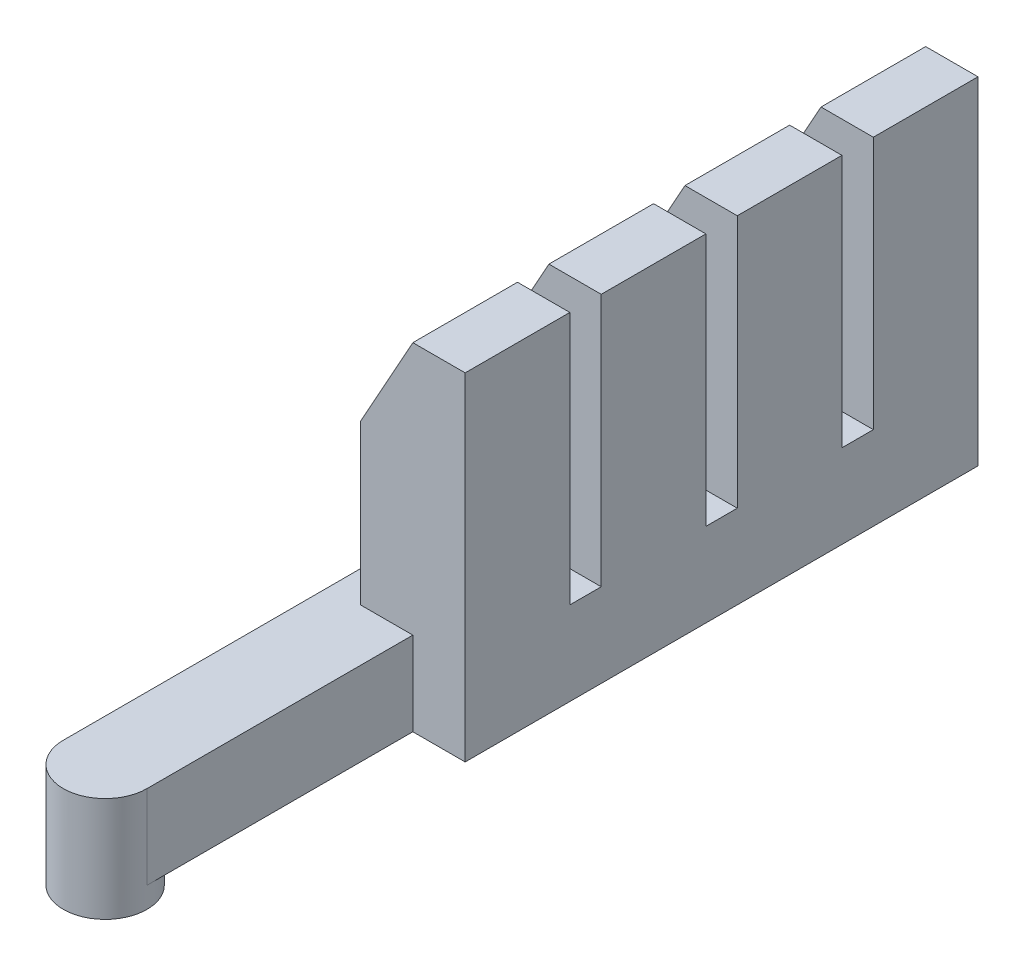
SolidWorks part; units mm, degrees
ref_plane "Front Plane" through (0, 0, 0) normal (0, 0, 1) x (1, 0, 0)
ref_plane "Top Plane" through (0, 0, 0) normal (0, 1, 0) x (1, 0, 0)
ref_plane "Right Plane" through (0, 0, 0) normal (1, 0, 0) x (0, 0, -1)
sketch "Sketch2" plane through (0, 0, 0) normal (0, 1, 0) x (1, 0, 0)
  circle A0 centre (0, 0) radius 20
  circle A1 centre (0, 0) radius 10
  dimension "D1" = 40
  dimension "D2" = 20
extrude "Boss-Extrude1" add sketch "Sketch2" along normal blind 80
sketch "Sketch3" plane through (0, 80, 0) normal (0, 1, 0) x (1, 0, 0)
  circle A0 centre (0, 0) radius 20
extrude "Boss-Extrude2" add sketch "Sketch3" along normal blind 5
sketch "Sketch4" plane through (0, 0, 0) normal (0, 0, 1) x (1, 0, 0)
  line L1 (20, 85) -> (-20, 85)
  line L2 (20, 85) -> (20, 45)
  line L3 (20, 45) -> (-20, 45)
  line L4 (-20, 85) -> (-20, 45)
  line L6 (15, 80) -> (-15, 80)
  line L7 (15, 80) -> (15, 50)
  line L8 (15, 50) -> (-15, 50)
  line L9 (-15, 80) -> (-15, 50)
  dimension "D1" = 40
  dimension "D2" = 5
  dimension "D3" = 5
  dimension "D4" = 5
  dimension "D5" = 5
extrude "Cut-Extrude1" cut sketch "Sketch4" against normal blind 50 contours L6 L9 L8 L7 | L7 L6 L9 L8 region at (0, 65, 0)
extrude "Boss-Extrude3" add sketch "Sketch4<4>" against normal blind 127 contours L1 L4 L3 L2 L9 L6 L7 L8 region at (19.4343, 65, 0)
sketch "Sketch4<4>" plane through (0, 0, 0) normal (0, 0, 1) x (1, 0, 0) same geometry as "Sketch4"
extrude "Cut-Extrude2" cut sketch "Sketch4<5>" along normal blind 10 contours L6 L9 L8 L7 region at (0, 65, 0)
sketch "Sketch4<5>" plane through (0, 0, 0) normal (0, 0, 1) x (1, 0, 0) same geometry as "Sketch4"
sketch "Sketch5" plane through (0, 0, 0) normal (0, -1, 0) x (1, 0, 0)
  circle A0 centre (0, 0) radius 10
extrude "Cut-Extrude3" cut sketch "Sketch5" against normal blind 50
sketch "Sketch6" plane through (0, 0, -127) normal (0, 0, -1) x (-1, 0, 0)
  line L0 (0, 80) -> (0, 85)
  line L1 (-15, 80) -> (15, 80) construction
  line L2 (-20, 85) -> (20, 85) construction
  line L3 (0, 85) -> (20, 85)
  line L4 (20, 85) -> (20, 45)
  line L5 (-20, 45) -> (20, 45) construction
  line L6 (-20, 45) -> (20, 45) construction
  line L7 (20, 45) -> (-45, 45)
  line L8 (-45, 45) -> (-45, 85)
  line L9 (-45, 85) -> (-40, 85)
  line L10 (-40, 85) -> (-40, 49.7955)
  line L11 (-40, 49.7955) -> (15, 50)
  line L12 (15, 50) -> (15, 80)
  line L13 (15, 80) -> (0, 80)
  dimension "D1" = 65
  dimension "D2" = 5
extrude "Boss-Extrude4" add sketch "Sketch6" along normal blind 245
sketch "Sketch7" plane through (0.1857, 49.9435, 0) normal (0.0037, 1, 0) x (1, -0.0037, 0)
  line L0 (-15.1858, 372) -> (-15.1858, 127) construction
  line L5 (39.8146, 127) -> (14.8146, 127)
  line L6 (39.8146, 127) -> (39.8146, 132)
  line L7 (39.8146, 132) -> (14.8146, 132)
  line L8 (14.8146, 127) -> (14.8146, 132)
  line L9 (39.8146, 372) -> (-15.1858, 372)
  line L10 (39.8146, 372) -> (39.8146, 367)
  line L11 (39.8146, 367) -> (-15.1858, 367)
  line L12 (-15.1858, 372) -> (-15.1858, 367)
  dimension "D1" = 25
  dimension "D2" = 5
  dimension "D3" = 5
extrude "Boss-Extrude5" add sketch "Sketch7" along normal blind 35
sketch "Sketch9" plane through (0, 85, 0) normal (0, 1, 0) x (1, 0, 0)
  line L1 (-5, 177) -> (45, 177)
  line L2 (-5, 177) -> (-5, 127)
  line L3 (-5, 127) -> (45, 127)
  line L4 (45, 177) -> (45, 127)
  line L5 (45, 372) -> (45, 127) construction
  line L6 (-5, 242) -> (45, 242)
  line L7 (-5, 242) -> (-5, 192)
  line L8 (-5, 192) -> (45, 192)
  line L9 (45, 242) -> (45, 192)
  line L11 (-5, 307) -> (45, 307)
  line L12 (-5, 307) -> (-5, 257)
  line L13 (-5, 257) -> (45, 257)
  line L14 (45, 307) -> (45, 257)
  line L15 (-5, 372) -> (45, 372)
  line L16 (-5, 372) -> (-5, 322)
  line L17 (-5, 322) -> (45, 322)
  line L18 (45, 372) -> (45, 322)
  line L19 (0, 172) -> (40, 172)
  line L20 (0, 172) -> (0, 132)
  line L21 (0, 132) -> (40, 132)
  line L22 (40, 172) -> (40, 132)
  line L23 (0, 237) -> (40, 237)
  line L24 (0, 237) -> (0, 197)
  line L25 (0, 197) -> (40, 197)
  line L26 (40, 237) -> (40, 197)
  line L27 (0, 302) -> (40, 302)
  line L28 (0, 302) -> (0, 262)
  line L29 (0, 262) -> (40, 262)
  line L30 (40, 302) -> (40, 262)
  line L31 (0, 367) -> (40, 367)
  line L32 (0, 367) -> (0, 327)
  line L33 (0, 327) -> (40, 327)
  line L34 (40, 367) -> (40, 327)
  line M36 (0, 127) -> (0, 372)
  dimension "D1" = 50
  dimension "D2" = 50
  dimension "D3" = 50
  dimension "D4" = 50
  dimension "D5" = 15
  dimension "D6" = 15
  dimension "D7" = 5
  dimension "D8" = 5
  dimension "D9" = 5
  dimension "D10" = 5
  dimension "D11" = 5
  dimension "D12" = 40
  dimension "D13" = 5
  dimension "D14" = 50
  dimension "D15" = 50
  dimension "D16" = 40
  dimension "D17" = 50
  dimension "D18" = 40
  dimension "D19" = 5
  dimension "D20" = 5
  dimension "D21" = 5
  dimension "D22" = 50
  dimension "D23" = 5
  dimension "D24" = 5
  dimension "D25" = 5
  dimension "D26" = 5
sketch "Sketch10" plane through (40, 0, 0) normal (-1, 0, 0) x (0, 0, 1)
  line L0 (-132, 84.7957) -> (-132, 49.7955) construction
  line L1 (-172, 85) -> (-197, 85)
  line L2 (-172, 85) -> (-172, 80)
  line L3 (-172, 80) -> (-197, 80)
  line L4 (-197, 85) -> (-197, 80)
  dimension "D1" = 25
  dimension "D2" = 5
  dimension "D3" = 40
sketch "Sketch11" plane through (0, 0, -372) normal (0, 0, -1) x (-1, 0, 0)
  line L0 (20, 45) -> (20, 85) construction
  line L1 (-45, 85) -> (20, 85)
  line L2 (-45, 85) -> (-45, 80)
  line L3 (-45, 80) -> (20, 80)
  line L4 (20, 85) -> (20, 80)
  dimension "D1" = 5
extrude "Boss-Extrude9" add sketch "Sketch11" against normal blind 245
extrude "Cut-Extrude4" cut sketch "Sketch9" against normal blind 10 contours L22 L19 L21 M36 | L26 L23 L25 M36 | L30 L27 L29 M36 | L34 L31 L33 M36 region at (20, 85, -152) region at (20, 85, -217) region at (20, 85, -282) region at (20, 85, -347)
extrude "Boss-Extrude10" add sketch "Sketch9<4>" along normal blind 116
sketch "Sketch9<4>" plane through (0, 85, 0) normal (0, 1, 0) x (1, 0, 0) same geometry as "Sketch9"
sketch "Sketch13" plane through (0, 201, 0) normal (0, 1, 0) x (1, 0, 0)
  line L0 (-5, 322) -> (45, 322) construction
  line L1 (45, 127) -> (-5, 127)
  line L2 (45, 127) -> (45, 177)
  line L3 (45, 177) -> (-5, 177)
  line L4 (-5, 127) -> (-5, 177)
  line L5 (45, 192) -> (-5, 192)
  line L6 (45, 192) -> (45, 242)
  line L7 (45, 242) -> (-5, 242)
  line L8 (-5, 192) -> (-5, 242)
  line L9 (45, 257) -> (-5, 257)
  line L10 (45, 257) -> (45, 307)
  line L11 (45, 307) -> (-5, 307)
  line L12 (-5, 257) -> (-5, 307)
  line L13 (45, 322) -> (-5, 322)
  line L14 (45, 322) -> (45, 372)
  line L15 (45, 372) -> (-5, 372)
  line L16 (-5, 322) -> (-5, 372)
  line L17 (-5, 322) -> (45, 322) construction
extrude "Boss-Extrude11" add sketch "Sketch13" along normal blind 5
sketch "Sketch14" plane through (-5, 0, 0) normal (-1, 0, 0) x (0, 0, 1)
  line L0 (-372, 206) -> (-372, 85) construction
  line L1 (-367, 201) -> (-327, 201)
  line L2 (-367, 201) -> (-367, 161)
  line L3 (-367, 161) -> (-327, 161)
  line L4 (-327, 201) -> (-327, 161)
  line L17 (-372, 206) -> (-322, 206) construction
  line L19 (-302, 201) -> (-262, 201)
  line L20 (-302, 201) -> (-302, 161)
  line L21 (-302, 161) -> (-262, 161)
  line L22 (-262, 201) -> (-262, 161)
  line L23 (-237, 201) -> (-197, 201)
  line L24 (-237, 201) -> (-237, 161)
  line L25 (-237, 161) -> (-197, 161)
  line L26 (-197, 201) -> (-197, 161)
  line L27 (-172, 201) -> (-132, 201)
  line L28 (-172, 201) -> (-172, 161)
  line L29 (-172, 161) -> (-132, 161)
  line L30 (-132, 201) -> (-132, 161)
  dimension "D1" = 40
  dimension "D2" = 5
  dimension "D3" = 5
  dimension "D4" = 40
  dimension "D5" = 4
extrude "Cut-Extrude5" cut sketch "Sketch14" against normal blind 5
sketch "Sketch15" plane through (0, 0, -372) normal (0, 0, -1) x (-1, 0, 0)
  line L6 (-20, 206) -> (5, 161)
  line L7 (-45, 206) -> (5, 206) construction
  line L8 (5, 206) -> (5, 85) construction
  line L9 (5, 161) -> (5, 206)
  line L10 (5, 206) -> (-20, 206)
  line L11 (5, 201) -> (-17.2222, 201)
  line M9 (5, 85) -> (5, 206)
  dimension "D1" = 5
  dimension "D2" = 40
  dimension "D3" = 25
extrude "Cut-Extrude6" cut sketch "Sketch15" against normal through all contours L11 L6 M9 | L10 L6 L9 region at (2.4074, 187.6667, -372)
sketch "Sketch16" plane through (-20, 0, 0) normal (-1, 0, 0) x (0, 0, 1)
  line L10 (-20, 45) -> (-20, 0) construction
  line L11 (-20, 35) -> (20, 35)
  line L12 (-20, 35) -> (-20, 0)
  line L13 (-20, 0) -> (20, 0)
  line L14 (20, 35) -> (20, 0)
  dimension "D1" = 35
extrude "Cut-Extrude7" cut sketch "Sketch16" against normal through all both and the other way through all
